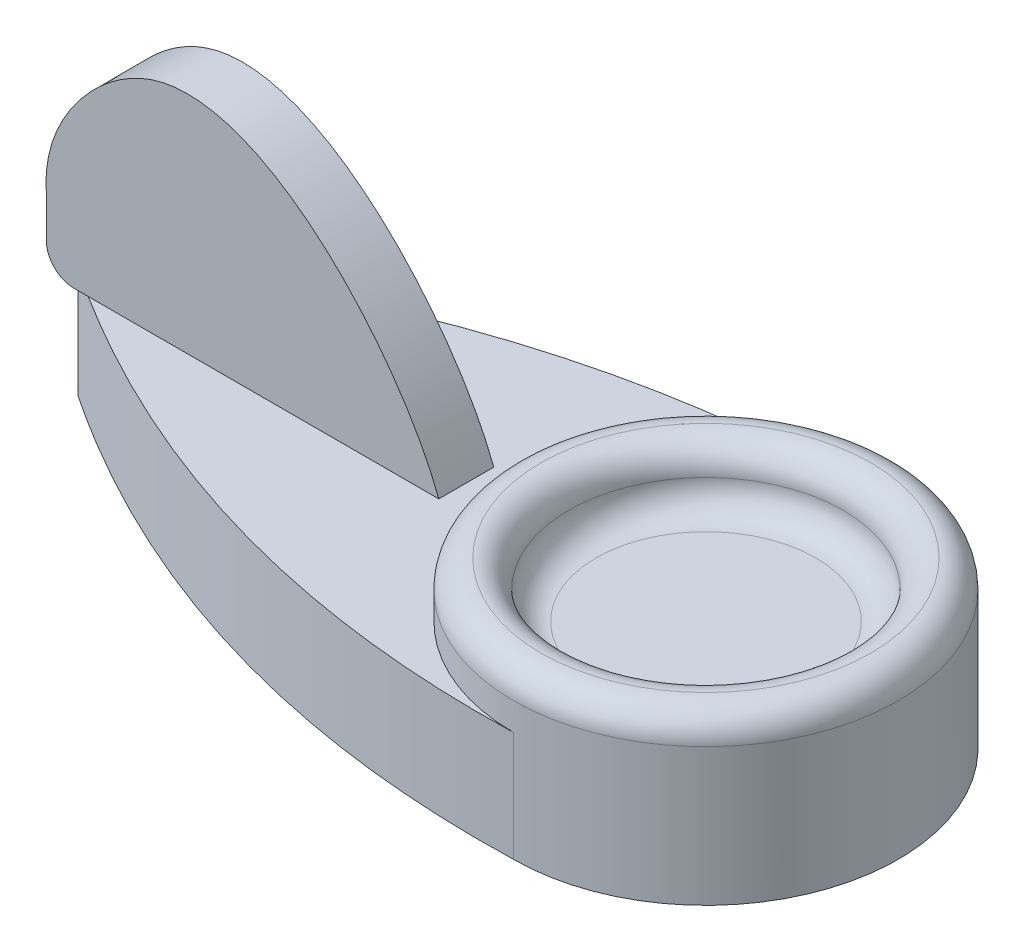
SolidWorks part; units mm, degrees
ref_plane "Front Plane" through (0, 0, 0) normal (0, 0, 1) x (1, 0, 0)
ref_plane "Top Plane" through (0, 0, 0) normal (0, 1, 0) x (1, 0, 0)
ref_plane "Right Plane" through (0, 0, 0) normal (1, 0, 0) x (0, 0, -1)
sketch "Sketch1" plane through (0, 0, 0) normal (0, 1, 0) x (1, 0, 0)
  line L0 (0, 0) -> (-11.5, 0) construction
  circle A0 centre (0, 0) radius 3.5
  spline S0 degree 2 poles (0, 3.5) (-6.1266, 3.6819) (-11.5, 0) knots 0 0 0 1 1 1
  spline S1 degree 2 poles (0, -3.5) (-6.1266, -3.6819) (-11.5, 0) knots 0 0 0 1 1 1
  point P6 (-2.2568, 3.4337)
  dimension "D1" = 11.5
  dimension "D2" = 7
extrude "Boss-Extrude1" add sketch "Sketch1" along normal blind 2 contours A0 | L0 A0 S0 | A0 L0 S1 region at (-5.9161, 0, 1.4141) region at (-5.9161, 0, -1.4141) region at (-2.4049, 0, -2.4049)
sketch "Sketch2" plane through (0, 2, 0) normal (0, 1, 0) x (1, 0, 0)
  circle A0 centre (0, 0) radius 3.5 construction
  circle A1 centre (0, 0) radius 3.5
extrude "Extrude-Thin1" add sketch "Sketch2" along normal blind 1 thin thin type one direction reverse wall 1
fillet "Fillet1" radius 0.5 3 edges at (2.5, 2, 0) (2.5, 3, 0) (0, 3, 3.5)
sketch "Sketch3" plane through (0, 0, 0) normal (0, 0, 1) x (1, 0, 0)
  line L0 (-11.5, 2) -> (-11.5, 3.2512)
  line L1 (0, 2) -> (-11.5, 2) construction
  line L2 (-4.3598, 2) -> (-11.5, 2)
  spline S0 degree 3 poles (-11.5, 3.2512) (-11.5481, 3.8726) (-11.0898, 5.0359) (-8.1437, 7.3521) (-5.063, 3.8692) (-4.3598, 2) knots 0 0 0 0 0.18077 0.345433 1 1 1 1
  point P4 (-6.5606, 7.5734)
  point P6 (-8.8884, 8.4622)
  point P8 (-5.6295, 4.1029)
  point P10 (-9.56, 8.3061)
  point P12 (-6.5108, 6.2249)
  point P13 (-10.5764, 7.3623)
  point P16 (-10.2376, 8.1125)
  point P17 (-10.9152, 4.9907)
  point P18 (-4.962, 3.1757)
  dimension "D1" = 4
extrude "Boss-Extrude2" add sketch "Sketch3" along normal mid plane 1
fillet "Fillet2" radius 0.5 2 edges at (-11.5, 2, 0.25) (-11.5, 2, -0.25)
fillet "Fillet3" radius 0.2 1 edges at (-11.5, 1.25, 0)
sketch "Sketch4" plane through (0, 0, 0) normal (0, -1, 0) x (1, 0, 0)
  arc A0 (0, -3.5) -> (0, 3.5) centre (0, 0) ccw construction
  arc A1 (0, -3.5) -> (0, 3.5) centre (0, 0) ccw
  circle A2 centre (0, 0) radius 1
extrude "Boss-Extrude3" add sketch "Sketch4" along normal blind 1 contours A2 region at (0, 0, 0)
